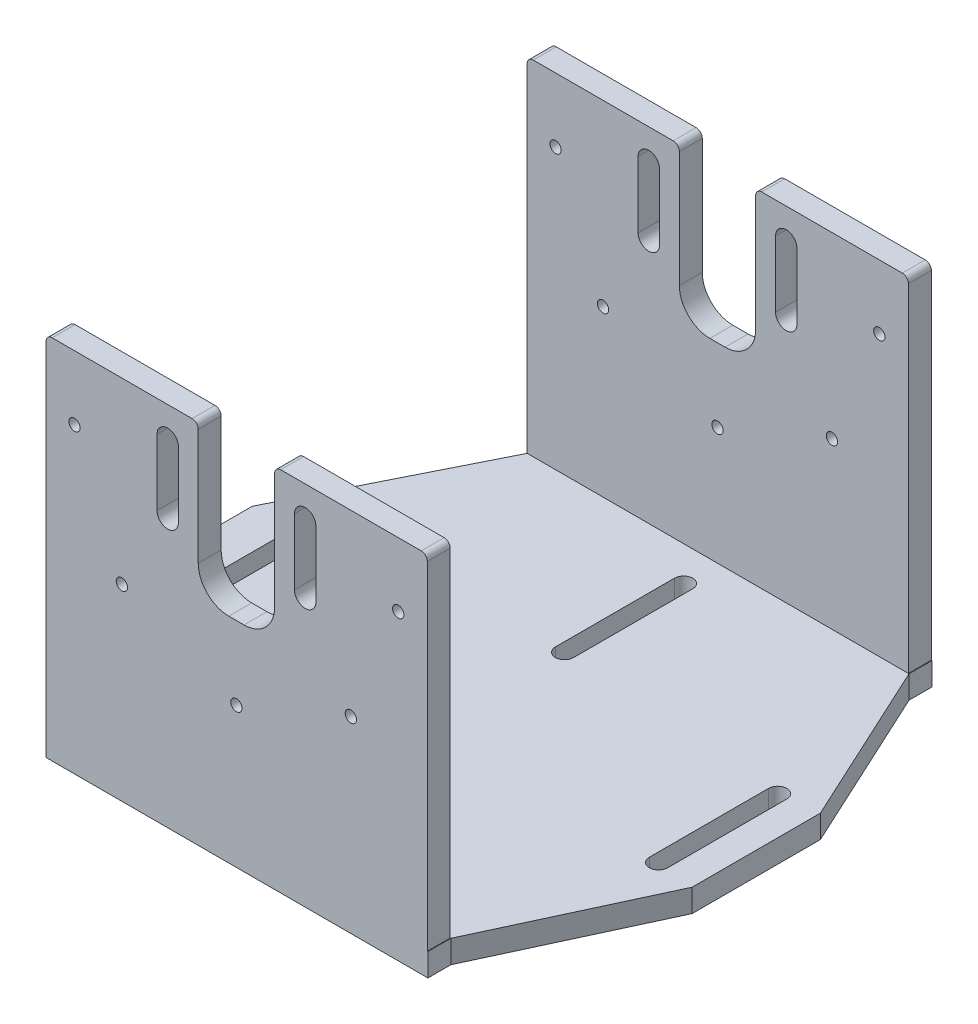
SolidWorks part; units mm, degrees
ref_plane "Front Plane" through (0, 0, 0) normal (0, 0, 1) x (1, 0, 0)
ref_plane "Top Plane" through (0, 0, 0) normal (0, 1, 0) x (1, 0, 0)
ref_plane "Right Plane" through (0, 0, 0) normal (1, 0, 0) x (0, 0, -1)
sketch "Sketch1" plane through (0, 0, 0) normal (0, 1, 0) x (1, 0, 0)
  line L8 (0, -7.5) -> (125, -7.5)
  line L10 (0, 157.5) -> (125, 157.5)
  line L12 (0, -7.5) -> (0, 0)
  line L14 (125, -7.5) -> (125, 0)
  line L15 (0, 157.5) -> (0, 150)
  line L16 (125, 157.5) -> (125, 150)
  line L17 (150, 54) -> (150, 96)
  line L18 (-30, 60) -> (-30, 90)
  line L19 (125, 150) -> (150, 96)
  line L20 (150, 54) -> (125, 0)
  line L21 (0, 0) -> (-30, 60)
  line L22 (-30, 90) -> (0, 150)
  line L23 (137.5, 55.5) -> (137.5, 94.5) construction
  line L24 (134.5, 55.5) -> (134.5, 94.5)
  line L25 (140.5, 55.5) -> (140.5, 94.5)
  line L26 (-14, 55.5) -> (-14, 94.5) construction
  line L27 (-17, 55.5) -> (-17, 94.5)
  line L28 (-11, 55.5) -> (-11, 94.5)
  line L29 (62.5, 11) -> (62.5, 50) construction
  line L30 (59.5, 11) -> (59.5, 50)
  line L31 (65.5, 11) -> (65.5, 50)
  line L32 (62.5, 138.7057) -> (62.5, 99.7057) construction
  line L33 (65.5, 138.7057) -> (65.5, 99.7057)
  line L34 (59.5, 138.7057) -> (59.5, 99.7057)
  arc A0 (134.5, 55.5) -> (140.5, 55.5) centre (137.5, 55.5) ccw
  arc A1 (140.5, 94.5) -> (134.5, 94.5) centre (137.5, 94.5) ccw
  arc A2 (-17, 55.5) -> (-11, 55.5) centre (-14, 55.5) ccw
  arc A3 (-11, 94.5) -> (-17, 94.5) centre (-14, 94.5) ccw
  arc A4 (59.5, 11) -> (65.5, 11) centre (62.5, 11) ccw
  arc A5 (65.5, 50) -> (59.5, 50) centre (62.5, 50) ccw
  arc A6 (65.5, 138.7057) -> (59.5, 138.7057) centre (62.5, 138.7057) ccw
  arc A7 (59.5, 99.7057) -> (65.5, 99.7057) centre (62.5, 99.7057) ccw
  point P18 (137.5, 75)
  point P23 (-14, 75)
  point P30 (62.5, 30.5)
  point P35 (62.5, 119.2057)
sketch "Sketch2" plane through (0, 0, 0) normal (0, 0, 1) x (1, 0, 0)
  line L1 (0, 0) -> (0, 118)
  line L9 (2, 120) -> (47.8128, 120)
  line L10 (49.8128, 118) -> (49.8128, 80)
  line L11 (59.8128, 70) -> (64.8128, 70)
  line L12 (74.8128, 80) -> (74.8128, 118)
  line L13 (76.8128, 120) -> (122.8128, 120)
  line L14 (124.8128, 118) -> (124.8128, 0)
  line L15 (0, 0) -> (124.8128, 0)
  line L16 (39.8128, 88.1904) -> (39.8128, 109.8096) construction
  line L17 (36.3128, 88.1904) -> (36.3128, 109.8096)
  line L18 (43.3128, 88.1904) -> (43.3128, 109.8096)
  line L20 (84.8128, 88.1904) -> (84.8128, 109.8096) construction
  line L21 (88.3128, 88.1904) -> (88.3128, 109.8096)
  line L22 (81.3128, 88.1904) -> (81.3128, 109.8096)
  arc A6 (59.8128, 70) -> (49.8128, 80) centre (59.8128, 80) cw
  arc A7 (64.8128, 70) -> (74.8128, 80) centre (64.8128, 80) ccw
  arc A8 (49.8128, 118) -> (47.8128, 120) centre (47.8128, 118) ccw
  arc A9 (76.8128, 120) -> (74.8128, 118) centre (76.8128, 118) ccw
  arc A10 (2, 120) -> (0, 118) centre (2, 118) ccw
  arc A11 (124.8128, 118) -> (122.8128, 120) centre (122.8128, 118) ccw
  arc A14 (36.3128, 88.1904) -> (43.3128, 88.1904) centre (39.8128, 88.1904) ccw
  arc A15 (43.3128, 109.8096) -> (36.3128, 109.8096) centre (39.8128, 109.8096) ccw
  arc A16 (88.3128, 88.1904) -> (81.3128, 88.1904) centre (84.8128, 88.1904) cw
  arc A17 (81.3128, 109.8096) -> (88.3128, 109.8096) centre (84.8128, 109.8096) cw
  circle A32 centre (115.2936, 99) radius 1.85
  circle A33 centre (99.7703, 61.5233) radius 1.85
  circle A34 centre (62.2936, 46) radius 1.85
  circle A36 centre (24.817, 61.5233) radius 1.85
  circle A53 centre (9.2936, 99) radius 1.85
  point P23 (49.8128, 99)
  point P24 (39.8128, 99)
  point P32 (84.8128, 99)
  point P117 (62.2936, 99)
  dimension "D3" = 2
  dimension "D4" = 2
  dimension "D5" = 2
  dimension "D6" = 2
extrude "Boss-Extrude6" add sketch "Sketch1" along normal blind 7.5
extrude "Boss-Extrude7" add sketch "Sketch2" along normal blind 7.5
ref_plane "Plane1" through (0, 0, -75) normal (0, 0, -1) x (-1, 0, 0)
mirror "Mirror1" about plane through (0, 0, -75) normal (0, 0, -1) of "Boss-Extrude7"
